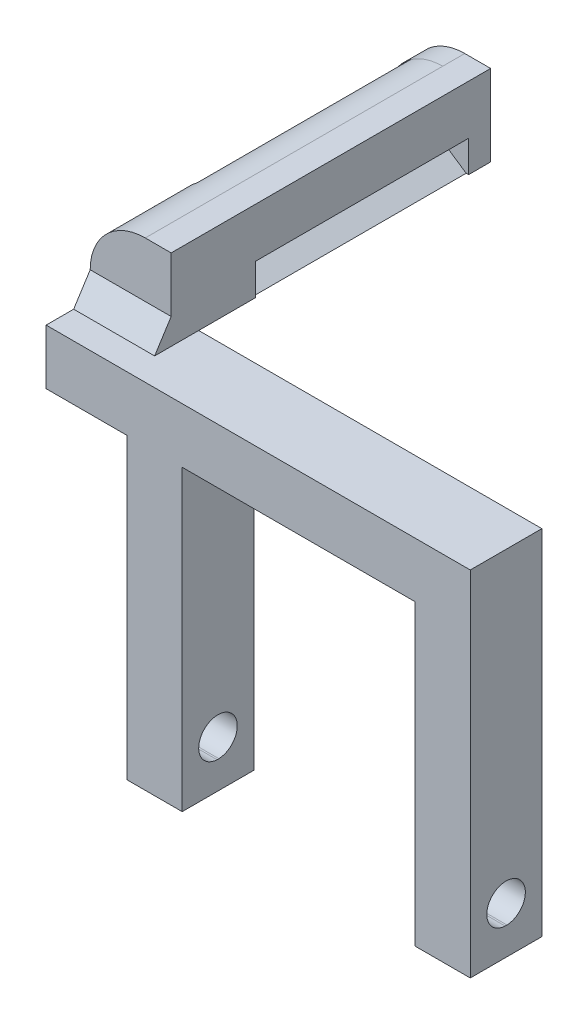
SolidWorks part; units mm, degrees
ref_plane "前基準面" through (0, 0, 0) normal (0, 0, 1) x (1, 0, 0)
ref_plane "上基準面" through (0, 0, 0) normal (0, 1, 0) x (1, 0, 0)
ref_plane "右基準面" through (0, 0, 0) normal (1, 0, 0) x (0, 0, -1)
sketch "草圖1" plane through (0, 0, 0) normal (0, 1, 0) x (1, 0, 0)
  line L1 (-21.5, 5) -> (21.5, 5)
  line L2 (-21.5, 5) -> (-21.5, -5)
  line L3 (-21.5, -5) -> (21.5, -5)
  line L4 (21.5, 5) -> (21.5, -5)
  line L5 (-21.5, 5) -> (21.5, -5) construction
  line L6 (-21.5, -5) -> (21.5, 5) construction
  point P0 (0, 0)
  dimension "D1" = 43
  dimension "D2" = 10
extrude "填料-伸長1" add sketch "草圖1" along normal blind 10
sketch "草圖2" plane through (21.5, 0, 0) normal (1, 0, 0) x (0, 0, -1)
  line L1 (-5, 10) -> (5, 10)
  line L2 (-5, 10) -> (-5, 0)
  line L3 (-5, 0) -> (5, 0)
  line L4 (5, 10) -> (5, 0)
extrude "填料-伸長2" add sketch "草圖2" along normal blind 10
sketch "草圖3" plane through (0, 0, 0) normal (0, -1, 0) x (1, 0, 0)
  line L0 (-21.5, 5) -> (31.5, 5) construction
  line L1 (31.5, -5) -> (21.5, -5)
  line L2 (31.5, -5) -> (31.5, 5)
  line L3 (31.5, 5) -> (21.5, 5)
  line L4 (21.5, -5) -> (21.5, 5)
  dimension "D1" = 10
extrude "填料-伸長3" add sketch "草圖3" along normal blind 43.18
sketch "草圖4" plane through (-21.5, 0, 0) normal (-1, 0, 0) x (0, 0, 1)
  line L1 (-5, 0) -> (5, 0)
  line L2 (-5, 0) -> (-5, 10)
  line L3 (-5, 10) -> (5, 10)
  line L4 (5, 0) -> (5, 10)
extrude "填料-伸長4" add sketch "草圖4" along normal blind 10
sketch "草圖5" plane through (0, 0, 0) normal (0, -1, 0) x (1, 0, 0)
  line L0 (-31.5, 5) -> (21.5, 5) construction
  line L1 (-31.5, -5) -> (-21.5, -5)
  line L2 (-31.5, -5) -> (-31.5, 5)
  line L3 (-31.5, 5) -> (-21.5, 5)
  line L4 (-21.5, -5) -> (-21.5, 5)
  dimension "D1" = 10
extrude "填料-伸長5" add sketch "草圖5" along normal blind 43.18
sketch "草圖7" plane through (-31.5, 0, 0) normal (-1, 0, 0) x (0, 0, 1)
  line L0 (5, -43.18) -> (5, 10) construction
  line L1 (-5, 10) -> (5, 10)
  line L2 (-5, 10) -> (-5, 0)
  line L3 (-5, 0) -> (5, 0)
  line L4 (5, 10) -> (5, 0)
  dimension "D1" = 10
extrude "填料-伸長6" add sketch "草圖7" along normal blind 14.7
sketch "草圖8" plane through (0, 10, 0) normal (0, 1, 0) x (1, 0, 0)
  line L0 (-46.2, -5) -> (31.5, -5) construction
  line L1 (-46.2, 5) -> (-31.5, 5)
  line L2 (-46.2, 5) -> (-46.2, -5)
  line L3 (-46.2, -5) -> (-31.5, -5)
  line L4 (-31.5, 5) -> (-31.5, -5)
  dimension "D1" = 14.7
extrude "填料-伸長7" add sketch "草圖8" along normal blind 14.7
sketch "草圖9" plane through (0, 0, -5) normal (0, 0, -1) x (-1, 0, 0)
  line L0 (46.2, 24.7) -> (46.2, 0) construction
  line L1 (31.5, 24.7) -> (46.2, 24.7)
  line L2 (31.5, 24.7) -> (31.5, 10)
  line L3 (31.5, 10) -> (46.2, 10)
  line L4 (46.2, 24.7) -> (46.2, 10)
  dimension "D1" = 14.7
extrude "填料-伸長8" add sketch "草圖9" along normal blind 14.7
sketch "草圖10" plane through (0, 0, -19.7) normal (0, 0, -1) x (-1, 0, 0)
  line L1 (31.5, 24.7) -> (46.2, 24.7)
  line L2 (31.5, 24.7) -> (31.5, 10)
  line L3 (31.5, 10) -> (46.2, 10)
  line L4 (46.2, 24.7) -> (46.2, 10)
extrude "填料-伸長10" add sketch "草圖10" along normal blind 14.82
sketch "草圖11" plane through (0, 24.7, 0) normal (0, 1, 0) x (1, 0, 0)
  line L0 (-38.85, -5) -> (-38.85, 49) construction
  line L1 (-46.2, -5) -> (-31.5, -5) construction
  line L2 (-46.2, 34.52) -> (-46.2, -5) construction
  line L3 (-31.5, 34.52) -> (-46.2, 34.52)
  line L4 (-31.5, 34.52) -> (-31.5, 49)
  line L5 (-31.5, 49) -> (-46.2, 49)
  line L6 (-46.2, 34.52) -> (-46.2, 49)
  dimension "D1" = 54
  dimension "D2" = 0
extrude "填料-伸長11" add sketch "草圖11" against normal blind 14.82
fillet "圓角2" radius 10 1 edges at (-46.2, 24.7, -22)
sketch "草圖15" plane through (0, 0, -49) normal (0, 0, -1) x (-1, 0, 0)
  line L0 (31.5, 10.657) -> (32.0212, 9.88)
  line L1 (31.5, 9.88) -> (31.5, 24.7) construction
  line L2 (31.5, 9.88) -> (46.2, 9.88) construction
  line L3 (32.0212, 9.88) -> (31.5, 9.88)
  line L4 (31.5, 5) -> (31.5, 10) construction
  line L5 (31.5, 9.88) -> (31.5, 10.657)
extrude "除料-伸長1" cut sketch "草圖15" against normal blind 38.7
sketch "草圖16" plane through (-26.655, 17.8798, 0) normal (0.8305, -0.5571, 0) x (0, 0, -1)
  line L0 (10.3, -8.6974) -> (10.3, -9.4885)
  line L1 (10.3, -9.4885) -> (49, -9.4885)
  line L2 (49, -9.6329) -> (49, -8.6974) construction
  line L3 (49, -9.4885) -> (49, -8.6974)
  line L4 (49, -8.6974) -> (10.3, -8.6974)
extrude "除料-伸長2" cut sketch "草圖16" against normal through all
sketch "草圖17" plane through (0, 0, -49) normal (0, 0, -1) x (-1, 0, 0)
  line L1 (31.9407, 10) -> (46.2, 10)
  line L2 (31.9407, 10) -> (31.9407, 9.88)
  line L3 (31.9407, 9.88) -> (46.2, 9.88)
  line L4 (46.2, 10) -> (46.2, 9.88)
extrude "除料-伸長3" cut sketch "草圖17" against normal blind 38.7
sketch "草圖18" plane through (0, 0, -49) normal (0, 0, -1) x (-1, 0, 0)
  line L0 (31.5, 24.7) -> (31.5, 10)
  line L1 (31.5, 10) -> (46.2, 10)
  line L2 (46.2, 10) -> (46.2, 24.7)
  line L3 (46.2, 24.7) -> (31.5, 24.7)
extrude "填料-伸長13" add sketch "草圖18" along normal blind 4
sketch "草圖21" plane through (-5.2857, -7.8798, 0) normal (0.5571, 0.8305, 0) x (0.8305, -0.5571, 0)
  line L0 (-32.0964, 10.3) -> (-48.134, 10.3)
  line L1 (-48.134, 10.3) -> (-48.134, 49)
  line L2 (-48.134, 49) -> (-32.0964, 49)
  line L3 (-32.0964, 49) -> (-32.0964, 10.3)
extrude "除料-伸長4" cut sketch "草圖21" along normal blind 5
fillet "圓角3" radius 10 1 edges at (-46.2, 24.7, -51)
sketch "草圖24" plane through (0, 0, -5) normal (0, 0, -1) x (-1, 0, 0)
  line L1 (-31.5, 10) -> (-21.5, 10)
  line L2 (-31.5, 10) -> (-31.5, -43.18)
  line L3 (-31.5, -43.18) -> (-21.5, -43.18)
  line L4 (-21.5, 10) -> (-21.5, -43.18)
extrude "除料-伸長6" cut sketch "草圖24" against normal blind 13
sketch "草圖25" plane through (0, 0, -5) normal (0, 0, -1) x (-1, 0, 0)
  line L0 (21.5, 0) -> (21.5, -42.15) construction
  line L2 (21.5, -42.15) -> (31.5, -42.15)
  line L3 (21.5, -42.15) -> (21.5, -43.18)
  line L4 (21.5, -43.18) -> (31.5, -43.18)
  line L5 (31.5, -42.15) -> (31.5, -43.18)
  dimension "D1" = 42.15
extrude "除料-伸長7" cut sketch "草圖25" against normal through all
sketch "草圖26" plane through (0, 0, -5) normal (0, 0, -1) x (-1, 0, 0)
  line L0 (21.5, 0) -> (-20.8, 0) construction
  line L1 (-21.5, 0) -> (21.5, 0) construction
  line L3 (-20.8, 0) -> (-21.5, 0)
  line L4 (-20.8, 0) -> (-20.8, 10)
  line L5 (-20.8, 10) -> (-21.5, 10)
  line L6 (-21.5, 0) -> (-21.5, 10)
  dimension "D1" = 42.3
extrude "除料-伸長8" cut sketch "草圖26" against normal through all
sketch "草圖27" plane through (20.8, 0, 0) normal (1, 0, 0) x (0, 0, -1)
  line L1 (-5, 10) -> (5, 10)
  line L2 (-5, 10) -> (-5, 0)
  line L3 (-5, 0) -> (5, 0)
  line L4 (5, 10) -> (5, 0)
extrude "填料-伸長15" add sketch "草圖27" along normal blind 10
sketch "草圖28" plane through (0, 0, 0) normal (0, -1, 0) x (1, 0, 0)
  line L0 (-21.5, 5) -> (30.8, 5) construction
  line L1 (30.8, -5) -> (20.8, -5)
  line L2 (30.8, -5) -> (30.8, 5)
  line L3 (30.8, 5) -> (20.8, 5)
  line L4 (20.8, -5) -> (20.8, 5)
  dimension "D1" = 10
extrude "填料-伸長16" add sketch "草圖28" along normal blind 42.15
sketch "草圖30" plane through (30.8, 0, 0) normal (1, 0, 0) x (0, 0, -1)
  line L0 (-5, 10) -> (5, 10) construction
  line L1 (5, -42.15) -> (0, -42.15)
  line L2 (5, -42.15) -> (5, 10)
  line L3 (5, 10) -> (0, 10)
  line L4 (0, -42.15) -> (0, 10)
  dimension "D1" = 5
extrude "除料-伸長9" cut sketch "草圖30" against normal blind 89
sketch "草圖32" plane through (0, 0, 5) normal (0, 0, 1) x (1, 0, 0)
  line L0 (20.8, -42.15) -> (30.8, -42.15)
  line L1 (30.8, -42.15) -> (30.8, 10)
  line L2 (30.8, 10) -> (-46.2, 10)
  line L3 (-46.2, 10) -> (-46.2, 0)
  line L4 (-46.2, 0) -> (-31.5, 0)
  line L5 (-31.5, 0) -> (-31.5, -42.15)
  line L6 (-31.5, -42.15) -> (-21.5, -42.15)
  line L7 (-21.5, -42.15) -> (-21.5, 0)
  line L8 (-21.5, 0) -> (20.8, 0)
  line L9 (20.8, 0) -> (20.8, -42.15)
extrude "填料-伸長18" add sketch "草圖32" along normal blind 3
sketch "草圖33" plane through (-39.9737, 26.8139, 0) normal (0.8305, -0.5571, 0) x (0, 0, -1)
  line L1 (10.3, -6.4275) -> (49, -6.4275)
  line L2 (10.3, -6.4275) -> (10.3, -8.6974)
  line L3 (10.3, -8.6974) -> (49, -8.6974)
  line L4 (49, -6.4275) -> (49, -8.6974)
extrude "除料-伸長10" cut sketch "草圖33" against normal blind 3
sketch "草圖34" plane through (-46.2, 0, 0) normal (-1, 0, 0) x (0, 0, 1)
  line L0 (5, 14.7) -> (8, 10)
  line L1 (8, 10) -> (5, 10)
  line L2 (5, 10) -> (5, 14.7)
extrude "填料-伸長19" add sketch "草圖34" against normal blind 15
sketch "草圖35" plane through (0, 0, 5) normal (0, 0, -1) x (-1, 0, 0)
  line L1 (31.2, 14.7) -> (31.5, 14.7)
  line L2 (31.2, 14.7) -> (31.2, 10)
  line L3 (31.2, 10) -> (31.5, 10)
  line L4 (31.5, 14.7) -> (31.5, 10)
extrude "除料-伸長11" cut sketch "草圖35" against normal through all
sketch "草圖36" plane through (0, -42.15, 0) normal (0, -1, 0) x (1, 0, 0)
  line L1 (30.8, 0) -> (20.8, 0)
  line L2 (30.8, 0) -> (30.8, 8)
  line L3 (30.8, 8) -> (20.8, 8)
  line L4 (20.8, 0) -> (20.8, 8)
  line L5 (-21.5, 0) -> (-31.5, 0)
  line L6 (-21.5, 0) -> (-21.5, 8)
  line L7 (-21.5, 8) -> (-31.5, 8)
  line L8 (-31.5, 0) -> (-31.5, 8)
extrude "填料-伸長20" add sketch "草圖36" along normal blind 2
sketch "草圖38" plane through (0, -44.15, 0) normal (0, -1, 0) x (1, 0, 0)
  line L1 (30.8, 8) -> (20.8, 8)
  line L2 (30.8, 8) -> (30.8, 0)
  line L3 (30.8, 0) -> (20.8, 0)
  line L4 (20.8, 8) -> (20.8, 0)
  line L5 (-21.5, 8) -> (-31.5, 8)
  line L6 (-21.5, 8) -> (-21.5, 0)
  line L7 (-21.5, 0) -> (-31.5, 0)
  line L8 (-31.5, 8) -> (-31.5, 0)
extrude "填料-伸長21" add sketch "草圖38" along normal blind 5
sketch "草圖41" plane through (0, 0, 8) normal (0, 0, 1) x (1, 0, 0)
  line L0 (-46.2, 10) -> (-46.2, 0)
  line L1 (-46.2, 0) -> (-31.5, 0)
  line L2 (-31.5, 0) -> (-31.5, -49.15)
  line L3 (-31.5, -49.15) -> (-21.5, -49.15)
  line L4 (-21.5, -49.15) -> (-21.5, 0)
  line L5 (-21.5, 0) -> (20.8, 0)
  line L6 (20.8, 0) -> (20.8, -49.15)
  line L7 (20.8, -49.15) -> (30.8, -49.15)
  line L8 (30.8, -49.15) -> (30.8, 10)
  line L9 (30.8, 10) -> (-46.2, 10)
extrude "填料-伸長22" add sketch "草圖41" along normal blind 5
sketch "草圖45" plane through (-21.5, 0, 0) normal (1, 0, 0) x (0, 0, -1)
  line L0 (-6.5, 0) -> (-6.5, -42.15) construction
  line L1 (0, 0) -> (-13, 0) construction
  circle A0 centre (-6.5, -45.6538) radius 3.5
  dimension "D2" = 7
  dimension "D1" = 42.15
extrude "除料-伸長13" cut sketch "草圖45" against normal through all and the other way blind 75
sketch "草圖46" plane through (0, -49.15, 0) normal (0, -1, 0) x (1, 0, 0)
  line L1 (30.8, 13) -> (20.8, 13)
  line L2 (30.8, 13) -> (30.8, 0)
  line L3 (30.8, 0) -> (20.8, 0)
  line L4 (20.8, 13) -> (20.8, 0)
  line L5 (-21.5, 13) -> (-31.5, 13)
  line L6 (-21.5, 13) -> (-21.5, 0)
  line L7 (-21.5, 0) -> (-31.5, 0)
  line L8 (-31.5, 13) -> (-31.5, 0)
extrude "填料-伸長23" add sketch "草圖46" along normal blind 5
